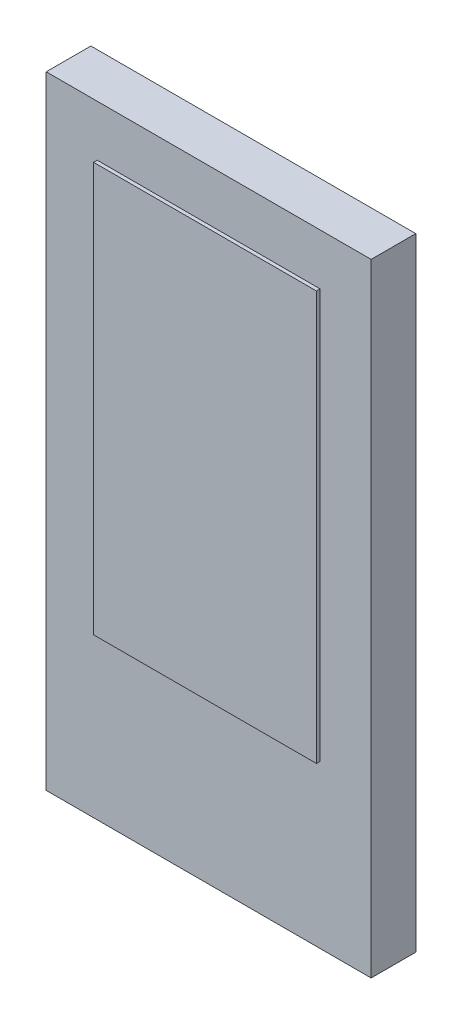
SolidWorks part; units mm, degrees
ref_plane "Plan de face" through (0, 0, 0) normal (0, 0, 1) x (1, 0, 0)
ref_plane "Plan de dessus" through (0, 0, 0) normal (0, 1, 0) x (1, 0, 0)
ref_plane "Plan de droite" through (0, 0, 0) normal (1, 0, 0) x (0, 0, -1)
sketch "Esquisse1" plane through (0, 0, 0) normal (0, 0, 1) x (1, 0, 0)
  line L1 (-4.464, -8.55) -> (4.464, -8.55)
  line L2 (-4.464, -8.55) -> (-4.464, 8.55)
  line L3 (-4.464, 8.55) -> (4.464, 8.55)
  line L4 (4.464, -8.55) -> (4.464, 8.55)
  line L5 (-4.464, -8.55) -> (4.464, 8.55) construction
  line L6 (-4.464, 8.55) -> (4.464, -8.55) construction
  point P0 (0, 0)
  dimension "D1" = 8.928
  dimension "D2" = 17.1
extrude "Boss.-Extru.1" add sketch "Esquisse1" along normal blind 1.227
sketch "Esquisse2" plane through (0, 0, 1.227) normal (0, 0, 1) x (1, 0, 0)
  line L0 (-4.464, -5.5) -> (4.464, -5.5) construction
  line L1 (-4.464, 8.55) -> (-4.464, -8.55) construction
  line L2 (4.464, -8.55) -> (4.464, 8.55) construction
  line L3 (4.464, 8.55) -> (-4.464, 8.55) construction
  line L4 (-4.464, 8.55) -> (4.464, -5.5) construction
  line L6 (-3.062, -4.097) -> (3.062, -4.097)
  line L7 (-3.062, -4.097) -> (-3.062, 7.147)
  line L8 (-3.062, 7.147) -> (3.062, 7.147)
  line L9 (3.062, -4.097) -> (3.062, 7.147)
  line L10 (-3.062, -4.097) -> (3.062, 7.147) construction
  line L11 (-3.062, 7.147) -> (3.062, -4.097) construction
  point P9 (0, 1.525)
  dimension "D1" = 14.05
  dimension "D2" = 6.124
  dimension "D3" = 11.244
extrude "Boss.-Extru.2" add sketch "Esquisse2" along normal blind 0.1
ref_plane "Plan1" through (0, 1.525, 0) normal (0, -1, 0) x (-1, 0, 0)
ref_plane "Plan2" through (0, 0, 0) normal (-1, 0, 0) x (0, 1, 0)
